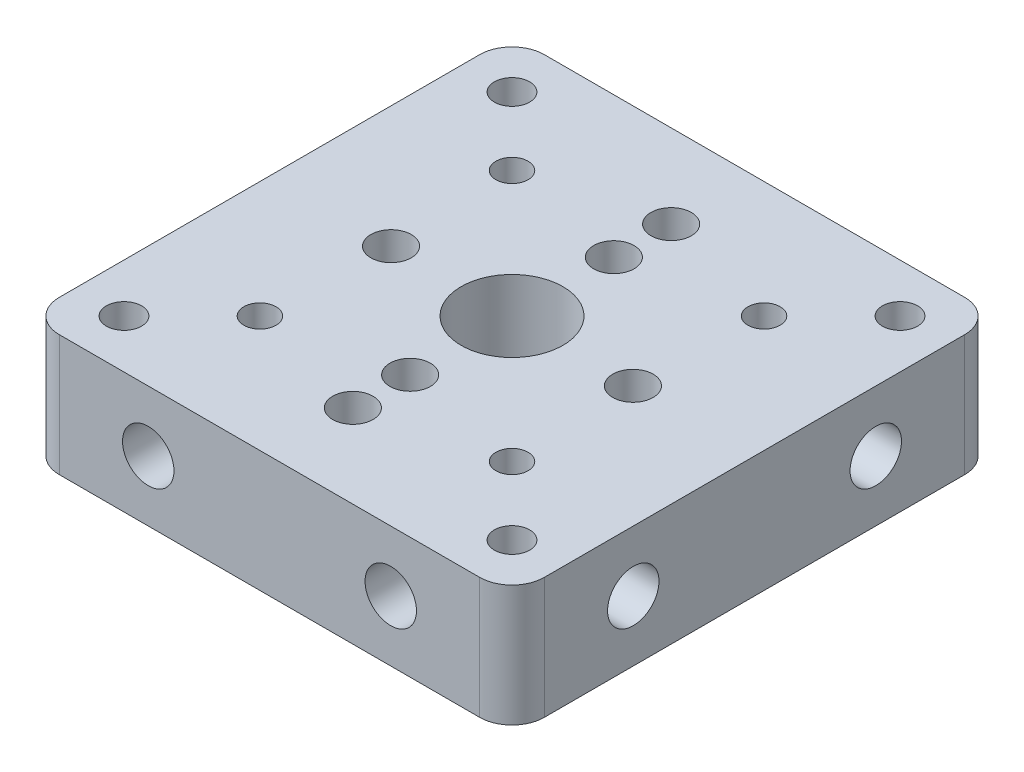
SolidWorks part; units mm, degrees
material "Alum Plate"
ref_plane "Front Plane" through (0, 0, 0) normal (0, 0, 1) x (1, 0, 0)
ref_plane "Top Plane" through (0, 0, 0) normal (0, 1, 0) x (1, 0, 0)
ref_plane "Right Plane" through (0, 0, 0) normal (1, 0, 0) x (0, 0, -1)
other "Bounding Box"
ref_plane "Default Plane" through (-8.9266, -12.7485, 0) normal (-0.1736, 0.9848, 0) x (0.9848, 0.1736, 0)
sketch "Sketch1" plane through (0, 0, 0) normal (0, 1, 0) x (1, 0, 0)
  line L0 (0, -12.5) -> (0, 12.5) construction
  line L2 (-19.05, 19.05) -> (19.05, 19.05)
  line L3 (-19.05, 19.05) -> (-19.05, -19.05)
  line L4 (-19.05, -19.05) -> (19.05, -19.05)
  line L5 (19.05, 19.05) -> (19.05, -19.05)
  line L6 (-19.05, 19.05) -> (19.05, -19.05) construction
  line L7 (-19.05, -19.05) -> (19.05, 19.05) construction
  point P3 (0, 0)
  circle B0 centre (-9.8995, -9.8995) radius 1.2645
  circle B1 centre (0, -8) radius 1.5875
  circle B2 centre (0, 0) radius 4
  circle B3 centre (9.8995, 9.8995) radius 1.2645
  circle B4 centre (0, 8) radius 1.5875
  circle B5 centre (9.8995, -9.8995) radius 1.2645
  circle B6 centre (0, -12.5) radius 1.5875
  circle B7 centre (-9.5, 0) radius 1.5875
  circle B8 centre (-15.24, 15.24) radius 1.3843
  circle B9 centre (15.24, 15.24) radius 1.3843
  circle B10 centre (15.24, -15.24) radius 1.3843
  circle B11 centre (-15.24, -15.24) radius 1.3843
  circle B12 centre (9.5, 0) radius 1.5875
  circle B13 centre (-9.8995, 9.8995) radius 1.2645
  circle B14 centre (0, 12.5) radius 1.5875
  dimension "D1" = 38.1
sketch_block_instance "Block-36mm gearbox motor block holes-1"
sketch_block "Block-36mm gearbox motor block holes"
extrude "Boss-Extrude1" add sketch "Sketch1" along normal mid plane 9.525
sketch "Sketch4" plane through (0, 0, 19.05) normal (0, 0, 1) x (1, 0, 0)
  line L0 (-9.525, 0) -> (0, 0) construction
  line L1 (0, 0) -> (9.525, 0) construction
  circle A0 centre (-9.525, 0) radius 2.0193
  circle A1 centre (9.525, 0) radius 2.0193
  dimension "D2" = 4.0386
  dimension "D1" = 19.05
extrude "Cut-Extrude2" cut sketch "Sketch4" against normal blind 9.525
pattern_circular "CirPattern1" count 4 over 360 about axis through (0, 4.7625, 0) along (0, -1, 0) of "Cut-Extrude2"
fillet "Fillet1" radius 2.54 4 edges at (-19.05, 0, 19.05) (-19.05, 0, -19.05) (19.05, 0, -19.05) (19.05, 0, 19.05)
